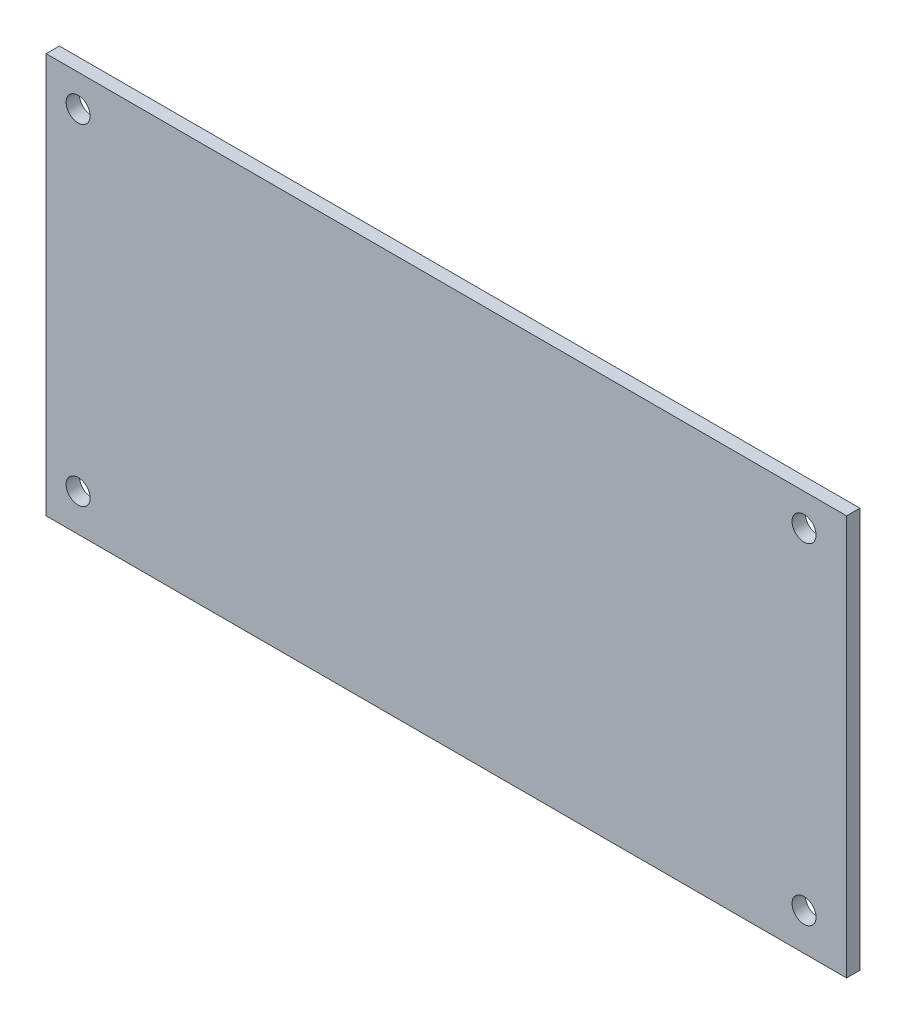
SolidWorks part; units mm, degrees
material "Epoxy, renforcé"
ref_plane "Plan de face" through (0, 0, 0) normal (0, 0, 1) x (1, 0, 0)
ref_plane "Plan de dessus" through (0, 0, 0) normal (0, 1, 0) x (1, 0, 0)
ref_plane "Plan de droite" through (0, 0, 0) normal (1, 0, 0) x (0, 0, -1)
sketch "Esquisse1" plane through (0, 0, 0) normal (0, 0, 1) x (1, 0, 0)
  line L1 (50, 25) -> (-50, 25)
  line L2 (50, 25) -> (50, -25)
  line L3 (50, -25) -> (-50, -25)
  line L4 (-50, 25) -> (-50, -25)
  line L5 (50, 25) -> (-50, -25) construction
  line L6 (50, -25) -> (-50, 25) construction
  line L7 (44.6841, 21) -> (-46, 21) construction
  line L8 (44.6841, 21) -> (44.6841, -20.342) construction
  line L9 (44.6841, -20.342) -> (-46, -20.342) construction
  line L10 (-46, 21) -> (-46, -20.342) construction
  line L11 (44.6841, 21) -> (-46, -20.342) construction
  line L12 (44.6841, -20.342) -> (-46, 21) construction
  circle A0 centre (-46, 21) radius 1.5
  circle A1 centre (-46, -20.342) radius 1.5
  circle A2 centre (44.6841, 21) radius 1.5
  circle A3 centre (44.6841, -20.342) radius 1.5
  point P0 (0, 0)
  point P6 (-0.658, 0.329)
  dimension "D5" = 3
  dimension "D6" = 3
  dimension "D7" = 3
  dimension "D8" = 3
  dimension "D1" = 50
  dimension "D2" = 100
  dimension "D3" = 4
  dimension "D4" = 4
extrude "Boss.-Extru.1" add sketch "Esquisse1" along normal blind 1.66
